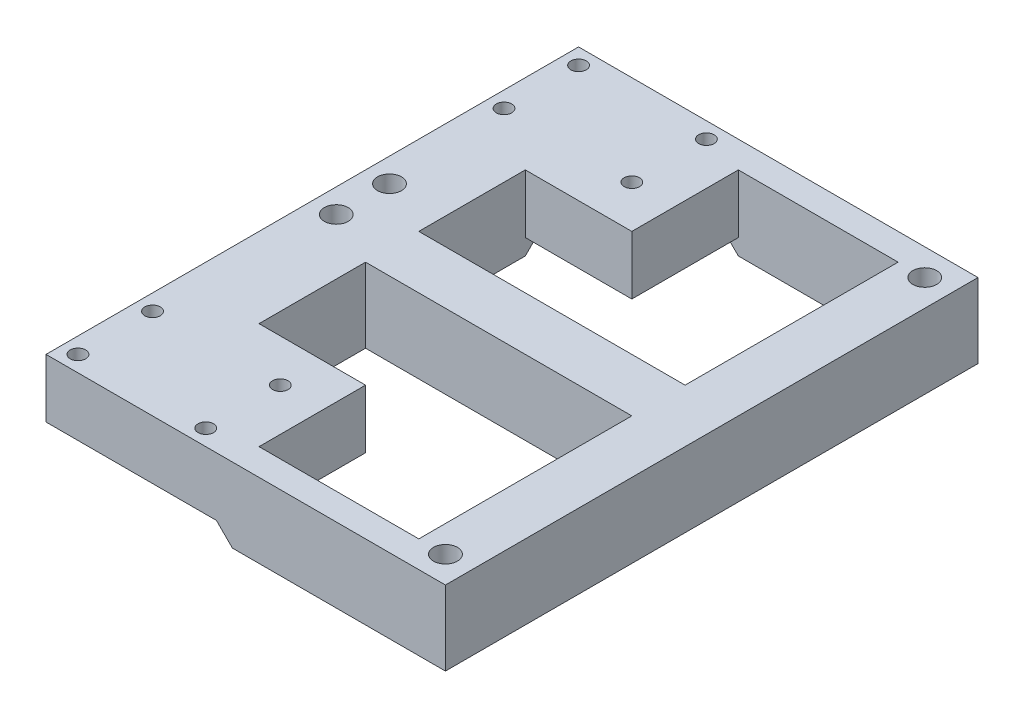
SolidWorks part; units mm, degrees
ref_plane "前视基准面" through (0, 0, 0) normal (0, 0, 1) x (1, 0, 0)
ref_plane "上视基准面" through (0, 0, 0) normal (0, 1, 0) x (1, 0, 0)
ref_plane "右视基准面" through (0, 0, 0) normal (1, 0, 0) x (0, 0, -1)
other "Configuration Table"
sketch "草图1" plane through (0, 0, 0) normal (0, 1, 0) x (1, 0, 0)
  line L1 (0, 0) -> (-75, 0)
  line L2 (0, 0) -> (0, 100)
  line L3 (0, 100) -> (-75, 100)
  line L4 (-75, 0) -> (-75, 100)
  dimension "D1" = 100
  dimension "D2" = 75
extrude "凸台-拉伸1" add sketch "草图1" along normal blind 16
sketch "草图6" plane through (0, 16, 0) normal (0, 1, 0) x (1, 0, 0)
  line L0 (-75, 100) -> (-75, 0) construction
  line L1 (-40, 45) -> (-5, 45)
  line L2 (-40, 25) -> (-40, 5)
  line L3 (-40, 5) -> (-5, 5)
  line L4 (-5, 45) -> (-5, 5)
  line L5 (0, 0) -> (0, 100) construction
  line L6 (-75, 0) -> (0, 0) construction
  line L7 (-75, 50) -> (-60.5255, 50) construction
  line L8 (-40, 95) -> (-5, 95)
  line L9 (-5, 55) -> (-5, 95)
  line L10 (-40, 55) -> (-5, 55)
  line L11 (-40, 75) -> (-40, 95)
  line L12 (-40, 75) -> (-70, 75)
  line L13 (-40, 45) -> (-70, 45)
  line L15 (-40, 25) -> (-70, 25)
  line L16 (-70, 45) -> (-70, 25)
  line L17 (-40, 55) -> (-70, 55)
  line L18 (-70, 55) -> (-70, 75)
  dimension "D1" = 35
  dimension "D2" = 5
  dimension "D3" = 5
  dimension "D4" = 40
  dimension "D5" = 30
  dimension "D6" = 20
extrude "切除-拉伸5" cut sketch "草图6" against normal up to next
sketch "草图8" plane through (0, 16, 0) normal (0, 1, 0) x (1, 0, 0)
  line L0 (-75, 100) -> (-72, 100) construction
  line L1 (0, 100) -> (-75, 100) construction
  line L2 (-72, 100) -> (-72, 97) construction
  line L3 (-72, 97) -> (-48, 97) construction
  line L4 (-48, 97) -> (-48, 83) construction
  line L5 (-48, 83) -> (-72, 83) construction
  line L6 (-75, 50) -> (-51.1245, 50) construction
  line L7 (-75, 100) -> (-75, 0) construction
  line L8 (-48, 17) -> (-72, 17) construction
  line L9 (-48, 3) -> (-48, 17) construction
  line L10 (-72, 3) -> (-48, 3) construction
  line L11 (-72, 0) -> (-72, 3) construction
  line L12 (-75, 0) -> (-72, 0) construction
  circle A0 centre (-72, 97) radius 1.45
  circle A1 centre (-72, 83) radius 1.45
  circle A2 centre (-48, 97) radius 1.45
  circle A3 centre (-48, 83) radius 1.45
  circle A4 centre (-48, 17) radius 1.45
  circle A5 centre (-48, 3) radius 1.45
  circle A6 centre (-72, 17) radius 1.45
  circle A7 centre (-72, 3) radius 1.45
  dimension "D6" = 2.9
  dimension "D7" = 2.9
  dimension "D8" = 2.9
  dimension "D9" = 2.9
  dimension "D1" = 3
  dimension "D2" = 3
  dimension "D3" = 24
  dimension "D4" = 14
  dimension "D5" = 24
extrude "切除-拉伸7" cut sketch "草图8" against normal through all
sketch "草图9" plane through (-5, 0, 0) normal (-1, 0, 0) x (0, 0, 1)
  line L0 (-45, 0) -> (-5, 0) construction
  line L1 (-5, 0) -> (-5, 16) construction
  line L2 (-5, 16) -> (-45, 16) construction
  line L3 (-45, 16) -> (-45, 0) construction
  line L4 (-95, 0) -> (-55, 0) construction
  line L5 (-55, 0) -> (-55, 16) construction
  line L6 (-55, 16) -> (-95, 16) construction
  line L7 (-95, 16) -> (-95, 0) construction
  line L8 (-45, 0) -> (-5, 0)
  line L9 (-5, 0) -> (-5, 16)
  line L10 (-5, 16) -> (-45, 16)
  line L11 (-45, 16) -> (-45, 0)
  line L12 (-95, 0) -> (-55, 0)
  line L13 (-55, 0) -> (-55, 16)
  line L14 (-55, 16) -> (-95, 16)
  line L15 (-95, 16) -> (-95, 0)
extrude "凸台-拉伸2" add sketch "草图9" along normal blind 5
sketch "草图10" plane through (0, 16, 0) normal (0, 1, 0) x (1, 0, 0)
  line L0 (0, 100) -> (0, 95) construction
  line L1 (0, 0) -> (0, 100) construction
  line L2 (0, 95) -> (-5, 95) construction
  line L3 (0, 50) -> (-16.1785, 50) construction
  circle A0 centre (-5, 95) radius 2.25
  circle A1 centre (-5, 5) radius 2.25
  dimension "D3" = 4.5
  dimension "D1" = 5
  dimension "D2" = 5
extrude "切除-拉伸8" cut sketch "草图10" against normal blind 5
sketch "草图11" plane through (0, 0, 0) normal (0, -1, 0) x (1, 0, 0)
  circle A0 centre (-5, -95) radius 2.25 construction
  circle A1 centre (-5, -5) radius 2.25 construction
  circle A2 centre (-5, -95) radius 2.25
  circle A3 centre (-5, -5) radius 2.25
extrude "切除-拉伸9" cut sketch "草图11" against normal blind 7
sketch "草图12" plane through (-70, 0, 0) normal (1, 0, 0) x (0, 0, -1)
  line L0 (25, 0) -> (45, 0) construction
  line L1 (45, 0) -> (45, 16) construction
  line L2 (45, 16) -> (25, 16) construction
  line L3 (25, 16) -> (25, 0) construction
  line L4 (55, 0) -> (75, 0) construction
  line L5 (75, 0) -> (75, 16) construction
  line L6 (75, 16) -> (55, 16) construction
  line L7 (55, 16) -> (55, 0) construction
  line L8 (25, 0) -> (45, 0)
  line L9 (45, 0) -> (45, 16)
  line L10 (45, 16) -> (25, 16)
  line L11 (25, 16) -> (25, 0)
  line L12 (55, 0) -> (75, 0)
  line L13 (75, 0) -> (75, 16)
  line L14 (75, 16) -> (55, 16)
  line L15 (55, 16) -> (55, 0)
extrude "凸台-拉伸3" add sketch "草图12" along normal blind 10
sketch "草图13" plane through (0, 16, 0) normal (0, 1, 0) x (1, 0, 0)
  line L0 (-75, 50) -> (-70.5, 50) construction
  line L1 (-75, 100) -> (-75, 0) construction
  line L3 (-70.5, 50) -> (-70.5, 60) construction
  circle A0 centre (-70.5, 50) radius 2.25
  circle A1 centre (-70.5, 60) radius 2.25
  dimension "D4" = 4.5
  dimension "D5" = 4.5
  dimension "D3" = 10
  dimension "D6" = 4.5
  dimension "D1" = 4.5
  dimension "D2" = 10
extrude "切除-拉伸10" cut sketch "草图13" against normal blind 5
sketch "草图14" plane through (0, 0, 0) normal (0, -1, 0) x (1, 0, 0)
  line L4 (0, -100) -> (0, 0)
  line L5 (0, 0) -> (-75, 0)
  line L6 (-75, 0) -> (-75, -100)
  line L7 (-75, -100) -> (0, -100)
  line L8 (0, -100) -> (0, 0)
  line L9 (0, 0) -> (-75, 0)
  line L10 (-75, 0) -> (-75, -100)
  line L11 (-75, -100) -> (0, -100)
  dimension "D1" = 0
extrude "切除-拉伸11" cut sketch "草图14" against normal blind 2
sketch "草图15" plane through (0, 11, 0) normal (0, 1, 0) x (1, 0, 0)
  circle A0 centre (-5, 5) radius 1.5
  circle A1 centre (-5, 95) radius 1.5
  circle A2 centre (-70.5, 60) radius 1.5
  circle A3 centre (-70.5, 50) radius 1.5
  dimension "D1" = 3
  dimension "D2" = 3
  dimension "D3" = 3
  dimension "D4" = 3
extrude "切除-拉伸12" cut sketch "草图15" against normal blind 4
sketch "草图16" plane through (0, 2, 0) normal (0, -1, 0) x (1, 0, 0)
  line L1 (-75, 0) -> (-40, 0)
  line L2 (-75, 0) -> (-75, -25)
  line L3 (-75, -25) -> (-40, -25)
  line L4 (-40, 0) -> (-40, -25)
  line L5 (-40, -75) -> (-75, -75)
  line L6 (-40, -75) -> (-40, -100)
  line L7 (-40, -100) -> (-75, -100)
  line L8 (-75, -75) -> (-75, -100)
extrude "切除-拉伸13" cut sketch "草图16" against normal blind 3
chamfer "倒角1" distance 3 angle 45 4 edges at (-40, 5, -2.5) (-67.5, 5, -25) (-67.5, 5, -75) (-40, 5, -97.5)
sketch "草图17" plane through (-75, 0, 0) normal (-1, 0, 0) x (0, 0, 1)
  line L0 (0, 9) -> (-55.4, 9) construction
  line L1 (0, 16) -> (0, 5) construction
  line L2 (-100, 16) -> (0, 16) construction
  circle A0 centre (-55.4, 9) radius 2.25
  point P5 (0, 0)
  dimension "D2" = 4.5
  dimension "D1" = 55.4
  dimension "D3" = 7
extrude "切除-拉伸14" cut sketch "草图17" against normal blind 5
sketch "草图18" plane through (-70, 0, 0) normal (-1, 0, 0) x (0, 0, 1)
  circle A0 centre (-55.4, 9) radius 1.5
  dimension "D1" = 3
extrude "切除-拉伸15" cut sketch "草图18" against normal blind 4
